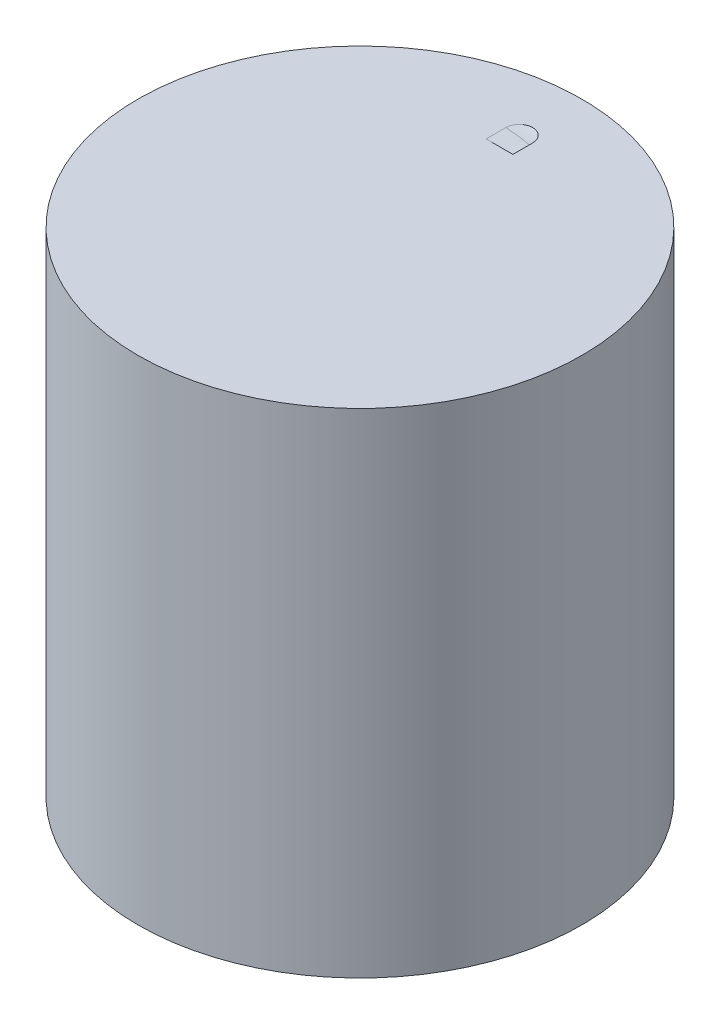
SolidWorks part; units mm, degrees
ref_plane "Front Plane" through (0, 0, 0) normal (0, 0, 1) x (1, 0, 0)
ref_plane "Top Plane" through (0, 0, 0) normal (0, 1, 0) x (1, 0, 0)
ref_plane "Right Plane" through (0, 0, 0) normal (1, 0, 0) x (0, 0, -1)
sketch "Sketch1" plane through (0, 0, 0) normal (0, 1, 0) x (1, 0, 0)
  circle A0 centre (0, 0) radius 45
  dimension "D1" = 90
extrude "Boss-Extrude1" add sketch "Sketch1" along normal blind 100
sketch "Sketch12" plane through (0, 100, 0) normal (0, 1, 0) x (1, 0, 0)
  line L2 (-2.7104, 32.2896) -> (-2.7104, 28.2896)
  line L3 (-2.7104, 28.2896) -> (2.7104, 28.2896)
  line L4 (2.7104, 32.2896) -> (2.7104, 28.2896)
  arc A0 (-2.7104, 32.2896) -> (2.7104, 32.2896) centre (0, 32.2896) cw
  point P6 (0, 35)
  point P9 (0, 0)
  point P10 (0, 0)
  dimension "D2" = 32.2896
  dimension "D1" = 4
  dimension "D3" = 35
sketch "Sketch15" plane through (0, 100, 0) normal (0, 1, 0) x (1, 0, 0)
  circle A0 centre (0, 0) radius 32.29
  dimension "D1" = 64.58
curve "Helix/Spiral2" pitch 30 height 120 radius 32.29 centre (0, 100, 0) axis (0, -1, 0) start towards (0, 0, 1)
sweep "Cut-Sweep3" cut profiles "Sketch12" path "Helix/Spiral2" align with end faces yes
